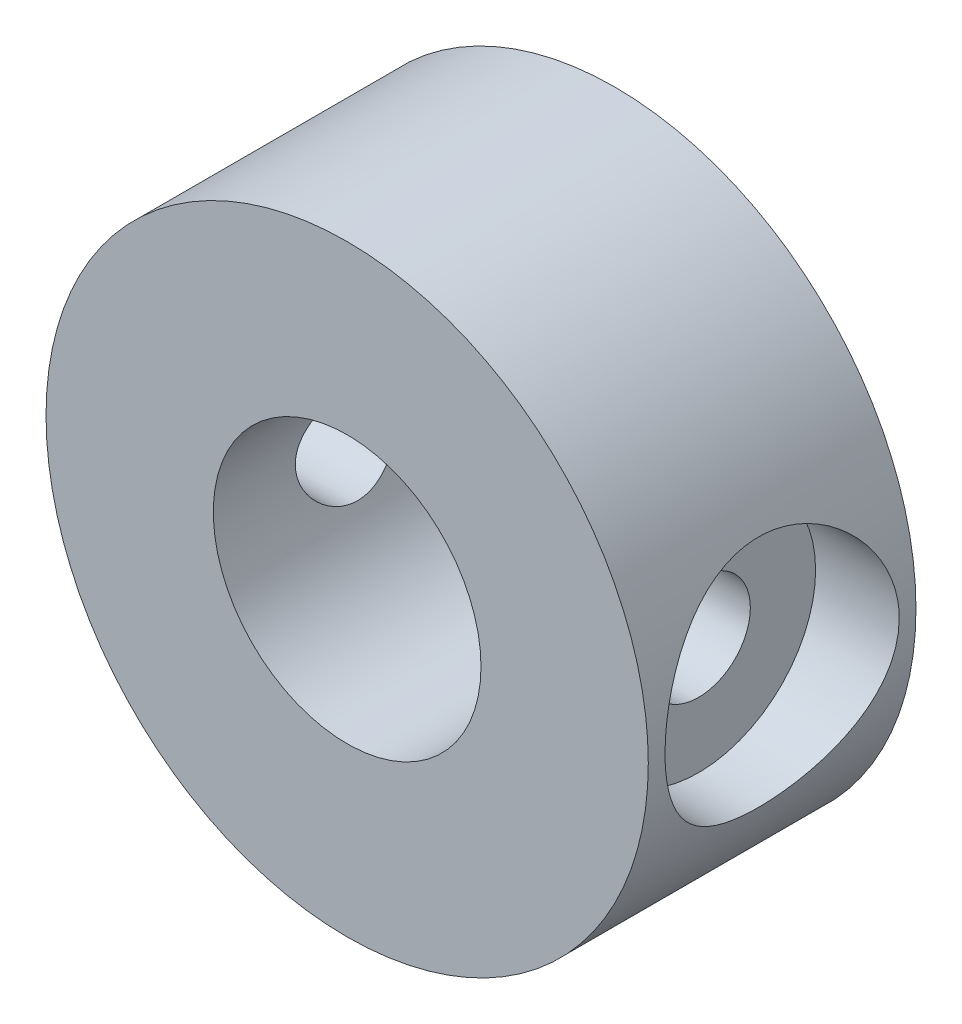
SolidWorks part; units mm, degrees
ref_plane "Front Plane" through (0, 0, 0) normal (0, 0, 1) x (1, 0, 0)
ref_plane "Top Plane" through (0, 0, 0) normal (0, 1, 0) x (1, 0, 0)
ref_plane "Right Plane" through (0, 0, 0) normal (1, 0, 0) x (0, 0, -1)
sketch "Sketch1" plane through (0, 0, 0) normal (0, 0, 1) x (1, 0, 0)
  circle A0 centre (0, 0) radius 4
  circle A1 centre (0, 0) radius 9
extrude "Boss-Extrude1" add sketch "Sketch1" along normal blind 8
ref_axis "Axis1" through (0, 0, 8) along (0, 0, -1)
ref_plane "Plane1" through (0, 0, 0) normal (1, 0, 0) x (0, 0, -1)
sketch "Sketch2" plane through (0, 0, 0) normal (1, 0, 0) x (0, 0, -1)
  line L0 (-8, 0) -> (0, 0) construction
  line L1 (-8, 9) -> (-8, -9) construction
  circle A0 centre (-4, 0) radius 1.55
extrude "Cut-Extrude1" cut sketch "Sketch2" against normal up to surface and the other way up to surface up to face at (9, 0, 8) other way up to face at (9, 0, 8)
sketch "Sketch3" plane through (0, 0, 0) normal (1, 0, 0) x (0, 0, -1)
  circle A0 centre (-4, 0) radius 3.5
extrude "Cut-Extrude3" cut sketch "Sketch3" against normal blind 2.5 from offset 9
extrude "Cut-Extrude4" cut sketch "Sketch3<3>" along normal blind 2.5 from offset 9 offset against normal yes
sketch "Sketch3<3>" plane through (0, 0, 0) normal (1, 0, 0) x (0, 0, -1) same geometry as "Sketch3"
